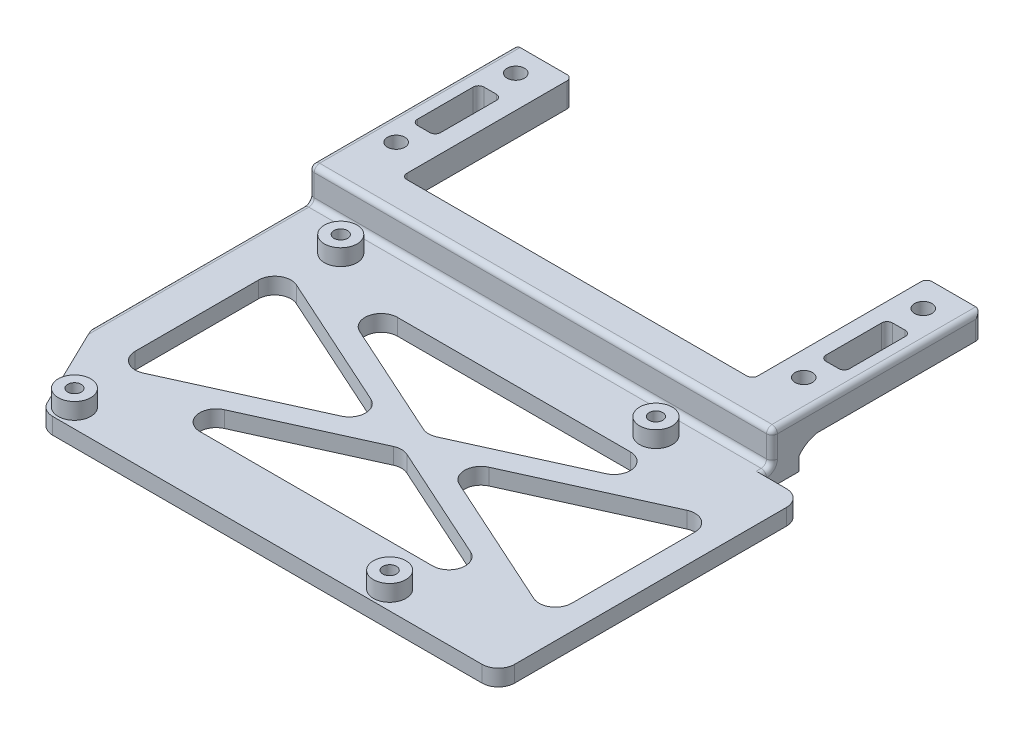
SolidWorks part; units mm, degrees
material "ABS"
ref_plane "Front Plane" through (0, 0, 0) normal (0, 0, 1) x (1, 0, 0)
ref_plane "Top Plane" through (0, 0, 0) normal (0, 1, 0) x (1, 0, 0)
ref_plane "Right Plane" through (0, 0, 0) normal (1, 0, 0) x (0, 0, -1)
other "Configuration Table"
sketch "Sketch1" plane through (0, 0, 0) normal (0, 1, 0) x (1, 0, 0)
  line B0 (-11.2928, -34.0981) -> (-11.2928, 51.3)
  line B1 (-11.2928, 51.3) -> (13.0597, 51.3)
  line B2 (13.0597, 51.3) -> (13.0597, 9.4086)
  line B3 (13.0597, 9.4086) -> (63.9139, 9.4086)
  line B4 (63.9139, 9.4086) -> (63.9139, 51.9)
  line B5 (63.9139, 51.9) -> (73.95, 51.9)
  line B6 (73.95, 51.9) -> (73.95, -34.0981)
  line B7 (73.95, -34.0981) -> (-11.2928, -34.0981)
  line B8 (-11.2928, -34.0981) -> (-3.2, -50.8077)
  circle B9 centre (-6.6, 46.8) radius 1.6
  circle B10 centre (-6.6, 24.8) radius 1.6
  circle B11 centre (68.4, 46.8) radius 1.6
  circle B12 centre (68.4, 24.8) radius 1.6
  line B13 (78.5, 3.5) -> (-0.5, 3.5)
  line B14 (81.5, -49.5) -> (81.5, 0.5)
  line B15 (-0.5, -52.5) -> (78.5, -52.5)
  line B16 (-3.5, 0.5) -> (-3.5, -49.5)
  circle B17 centre (0, -49) radius 1.25
  circle B18 centre (58, -49) radius 1.25
  circle B19 centre (58, 0) radius 1.25
  circle B20 centre (0, 0) radius 1.25
  arc B21 (81.5, 0.5) -> (78.5, 3.5) centre (78.5, 0.5) ccw
  arc B22 (78.5, -52.5) -> (81.5, -49.5) centre (78.5, -49.5) ccw
  arc B23 (-3.5, -49.5) -> (-0.5, -52.5) centre (-0.5, -49.5) ccw
  arc B24 (-0.5, 3.5) -> (-3.5, 0.5) centre (-0.5, 0.5) ccw
sketch_block_instance "Block2-1"
sketch_block "Block2"
sketch_block_instance "Block1-1"
sketch_block "Block1" parameters "D1"=2.7
extrude "Boss-Extrude1" add sketch "Sketch1" along normal blind 3 contours B13 B24 B16 B7 B6 B19 B20 | B16 B23 B15 B22 B14 B21 B13 B6 B7 B17 B18 | B23 B16 B7 B8 | B24 B13 B6 B5 B4 B3 B2 B1 B0 B7 B16 B12 B11 B10 B9
sketch "Sketch2" plane through (0, 3, 0) normal (0, 1, 0) x (1, 0, 0)
  line L0 (-0.6689, 51.3) -> (-0.6689, 9.4086)
  line L1 (-11.2928, 51.3) -> (13.0597, 51.3) construction
  line L2 (-0.6689, 9.4086) -> (13.0597, 9.4086)
  line L3 (-0.6689, 51.3) -> (13.0597, 51.3)
  line L4 (13.0597, 51.3) -> (13.0597, 9.4086)
extrude "Cut-Extrude1" cut sketch "Sketch2" against normal blind 3
sketch "Sketch3" plane through (0, 3, 0) normal (0, 1, 0) x (1, 0, 0)
  line L0 (-11.2928, 5.4086) -> (73.95, 5.4086)
  line L1 (-11.2928, -34.0981) -> (-11.2928, 51.3) construction
  line L2 (73.95, 51.9) -> (73.95, 3.5) construction
  line L3 (-0.6689, 9.4086) -> (63.9139, 9.4086) construction
  line L4 (-11.2928, 5.4086) -> (-11.2928, 9.4086)
  line L5 (-11.2928, 9.4086) -> (73.95, 9.4086)
  line L6 (73.95, 9.4086) -> (73.95, 5.4086)
  line L18 (63.9139, 9.4086) -> (-0.6689, 9.4086)
  line L19 (-0.6689, 9.4086) -> (-0.6689, 51.3)
  line L20 (-0.6689, 51.3) -> (-11.2928, 51.3)
  line L21 (-11.2928, 51.3) -> (-11.2928, -34.0981)
  line L22 (-11.2928, -34.0981) -> (-3.2, -50.8077)
  line L23 (-0.5, -52.5) -> (78.5, -52.5)
  line L24 (81.5, -49.5) -> (81.5, 0.5)
  line L25 (78.5, 3.5) -> (73.95, 3.5)
  line L26 (73.95, 3.5) -> (73.95, 51.9)
  line L27 (73.95, 51.9) -> (63.9139, 51.9)
  line L28 (63.9139, 51.9) -> (63.9139, 9.4086)
  line L29 (63.9139, 9.4086) -> (-0.6689, 9.4086)
  line L30 (-0.6689, 9.4086) -> (-0.6689, 51.3)
  line L31 (-0.6689, 51.3) -> (-11.2928, 51.3)
  line L32 (-11.2928, 51.3) -> (-11.2928, -34.0981)
  line L33 (-11.2928, -34.0981) -> (-3.2, -50.8077)
  line L34 (-0.5, -52.5) -> (78.5, -52.5)
  line L35 (81.5, -49.5) -> (81.5, 0.5)
  line L36 (78.5, 3.5) -> (73.95, 3.5)
  line L37 (73.95, 3.5) -> (73.95, 51.9)
  line L38 (73.95, 51.9) -> (63.9139, 51.9)
  line L39 (63.9139, 51.9) -> (63.9139, 9.4086)
  circle A1 centre (58, 0) radius 1.25
  circle A2 centre (58, 0) radius 1.25
  circle A3 centre (0, 0) radius 1.25
  circle A4 centre (0, 0) radius 1.25
  circle A5 centre (0, -49) radius 1.25
  circle A6 centre (0, -49) radius 1.25
  circle A7 centre (58, -49) radius 1.25
  circle A8 centre (58, -49) radius 1.25
  circle A9 centre (68.4, 24.8) radius 1.6
  circle A10 centre (68.4, 24.8) radius 1.6
  circle A11 centre (68.4, 46.8) radius 1.6
  circle A12 centre (68.4, 46.8) radius 1.6
  circle A13 centre (-6.6, 24.8) radius 1.6
  circle A14 centre (-6.6, 24.8) radius 1.6
  circle A15 centre (-6.6, 46.8) radius 1.6
  circle A16 centre (-6.6, 46.8) radius 1.6
  arc A19 (-3.2, -50.8077) -> (-0.5, -52.5) centre (-0.5, -49.5) ccw
  arc A20 (78.5, -52.5) -> (81.5, -49.5) centre (78.5, -49.5) ccw
  arc A21 (81.5, 0.5) -> (78.5, 3.5) centre (78.5, 0.5) ccw
  arc A22 (-3.2, -50.8077) -> (-0.5, -52.5) centre (-0.5, -49.5) ccw
  arc A23 (78.5, -52.5) -> (81.5, -49.5) centre (78.5, -49.5) ccw
  arc A24 (81.5, 0.5) -> (78.5, 3.5) centre (78.5, 0.5) ccw
  line M25 (63.9139, 9.4086) -> (-0.6689, 9.4086)
  line M26 (-0.6689, 9.4086) -> (-0.6689, 51.3)
  line M27 (-0.6689, 51.3) -> (-11.2928, 51.3)
  line M28 (-11.2928, 51.3) -> (-11.2928, -34.0981)
  line M36 (73.95, 3.5) -> (73.95, 51.9)
  line M37 (73.95, 51.9) -> (63.9139, 51.9)
  line M38 (63.9139, 51.9) -> (63.9139, 9.4086)
  circle M43 centre (68.4, 24.8) radius 1.6
  circle M44 centre (68.4, 46.8) radius 1.6
  circle M45 centre (-6.6, 24.8) radius 1.6
  circle M46 centre (-6.6, 46.8) radius 1.6
  dimension "D1" = 4
  dimension "D2" = 0
  dimension "D3" = 0
  dimension "D4" = 0
  dimension "D5" = 0
  dimension "D6" = 0
  dimension "D7" = 0
  dimension "D8" = 0
  dimension "D9" = 0
  dimension "D10" = 0
extrude "Boss-Extrude2" add sketch "Sketch3" along normal blind 6 contours L5 L0 M28 M36 M25 | L5 M28 M26 M27 M46 M45 | L5 M38 M36 M37 M43 M44
sketch "Sketch4" plane through (73.95, 0, 0) normal (1, 0, 0) x (0, 0, -1)
  line L0 (5.4086, 9) -> (5.4086, 3) construction
  line L1 (10.4086, 4.5) -> (51.9, 4.5)
  line L2 (10.4086, 4.5) -> (10.4086, 0)
  line L3 (10.4086, 0) -> (51.9, 0)
  line L4 (51.9, 4.5) -> (51.9, 0)
  line L5 (51.9, 9) -> (51.9, 0) construction
  point P4 (51.9, 4.5)
  dimension "D1" = 5
extrude "Cut-Extrude2" cut sketch "Sketch4" against normal blind 115
sketch "Sketch6" plane through (0, 9, 0) normal (0, 1, 0) x (1, 0, 0)
  line L0 (63.9139, 51.9) -> (63.9139, 9.4086) construction
  line L1 (-0.6689, 9.4086) -> (63.9139, 9.4086)
  line L2 (-0.6689, 9.4086) -> (-0.6689, 11.8232)
  line L3 (-0.6689, 11.8232) -> (63.9139, 11.8232)
  line L4 (63.9139, 9.4086) -> (63.9139, 11.8232)
extrude "Boss-Extrude3" add sketch "Sketch6" against normal up to surface (4.5 mm away) up to face at (-6.6, 4.5, -23.2)
sketch "Sketch7" plane through (0, 3, 0) normal (0, 1, 0) x (1, 0, 0)
  line L1 (-3.3072, -4.9906) -> (77.0194, -4.9906)
  line L2 (-3.3072, -4.9906) -> (-3.3072, -41.3669)
  line L3 (-3.3072, -41.3669) -> (77.0194, -41.3669)
  line L4 (77.0194, -4.9906) -> (77.0194, -41.3669)
extrude "Cut-Extrude3" cut sketch "Sketch7" against normal blind 115
sketch "Sketch9" plane through (0, 3, 0) normal (0, 1, 0) x (1, 0, 0)
  line L0 (-3.3072, -4.9906) -> (77.0194, -41.3669)
  line L1 (77.0194, -4.9906) -> (-3.3072, -41.3669)
extrude "Extrude-Thin1" add sketch "Sketch9" against normal up to surface (3 mm away) thin up to face at (36.8561, 0, 23.1787) thin type mid plane wall 4
fillet "Fillet2" radius 3 12 edges at (1.5409, 1.5, 41.3669) (72.1713, 1.5, 41.3669) (36.8561, 1.5, 25.3743) (77.0194, 1.5, 39.1714) (41.7043, 1.5, 23.1787) (77.0194, 1.5, 7.1861) (72.1713, 1.5, 4.9906) (36.8561, 1.5, 20.9832) (1.5409, 1.5, 4.9906) (32.0079, 1.5, 23.1787) (-3.3072, 1.5, 39.1714) (-3.3072, 1.5, 7.1861)
fillet "Fillet3" radius 1 6 edges at (73.95, 3, -4.4543) (31.3286, 3, -5.4086) (73.95, 6, -5.4086) (31.3286, 9, -5.4086) (-11.2928, 6, -5.4086) (-11.2928, 3, 14.3447)
sketch "Sketch10" plane through (0, 3, 0) normal (0, 1, 0) x (1, 0, 0)
  circle A0 centre (0, 0) radius 3
  circle A1 centre (58, 0) radius 3
  circle A2 centre (0, -49) radius 3
  circle A3 centre (58, -49) radius 3
  circle A4 centre (0, 0) radius 1.25 construction
  circle A5 centre (0, -49) radius 1.25 construction
  circle A6 centre (58, -49) radius 1.25 construction
  circle A7 centre (0, 0) radius 1.25
  circle A8 centre (0, -49) radius 1.25
  circle A9 centre (58, -49) radius 1.25
  circle A10 centre (58, 0) radius 1.25 construction
  circle A11 centre (58, 0) radius 1.25
  dimension "D1" = 6
extrude "Boss-Extrude4" add sketch "Sketch10" along normal blind 3
fillet "Fillet4" radius 5 1 edges at (31.6225, 4.5, -9.4086)
ref_plane "Plane1" through (0, 0, -14.4086) normal (0, 0, -1) x (-1, 0, 0)
sketch "Sketch13" plane through (0, 9, 0) normal (0, 1, 0) x (1, 0, 0)
  line L0 (-11.2928, 51.3) -> (-11.2928, 6.4086) construction
  line L1 (-11.2928, 21.495) -> (73.95, 21.495)
  line L2 (-11.2928, 21.495) -> (-11.2928, 13.495)
  line L3 (-11.2928, 13.495) -> (73.95, 13.495)
  line L4 (73.95, 21.495) -> (73.95, 13.495)
  line L5 (73.95, 6.4086) -> (73.95, 51.9) construction
  dimension "D1" = 8
extrude "Cut-Extrude5" cut sketch "Sketch13" against normal blind 12
move or copy body "Body-Move/Copy1" bodies to move or copy 113 112 copy no translate (0, 0, 8)
combine bodies "Combine1" operation type add bodies to combine 114 115 111
sketch "Sketch14" plane through (0, 9, 0) normal (0, 1, 0) x (1, 0, 0)
  line L1 (-8.3148, 33.6758) -> (-4.0462, 33.6758)
  line L2 (-8.3148, 33.6758) -> (-8.3148, 21.4319)
  line L3 (-8.3148, 21.4319) -> (-4.0462, 21.4319)
  line L4 (-4.0462, 33.6758) -> (-4.0462, 21.4319)
  line L5 (66.8589, 33.6758) -> (71.1992, 33.6758)
  line L6 (66.8589, 33.6758) -> (66.8589, 21.4319)
  line L7 (66.8589, 21.4319) -> (71.1992, 21.4319)
  line L8 (71.1992, 33.6758) -> (71.1992, 21.4319)
extrude "Cut-Extrude6" cut sketch "Sketch14" against normal blind 12
fillet "Fillet5" radius 1 8 edges at (-4.0462, 6.75, -21.4319) (-8.3148, 6.75, -21.4319) (-8.3148, 6.75, -33.6758) (-4.0462, 6.75, -33.6758) (71.1992, 6.75, -21.4319) (66.8589, 6.75, -21.4319) (66.8589, 6.75, -33.6758) (71.1992, 6.75, -33.6758)
fillet "Fillet6" radius 1 10 edges at (-11.2928, 9, -24.8543) (73.95, 6.75, -43.9) (-0.6689, 6.75, -43.3) (73.95, 9, -25.1543) (63.9139, 6.3973, -11.8232) (63.9139, 6.75, -43.9) (-11.2928, 6.75, -43.3) (-0.6689, 6.3973, -11.8232) (-10.9999, 8.7071, -5.7015) (73.6571, 8.7071, -5.7015)
